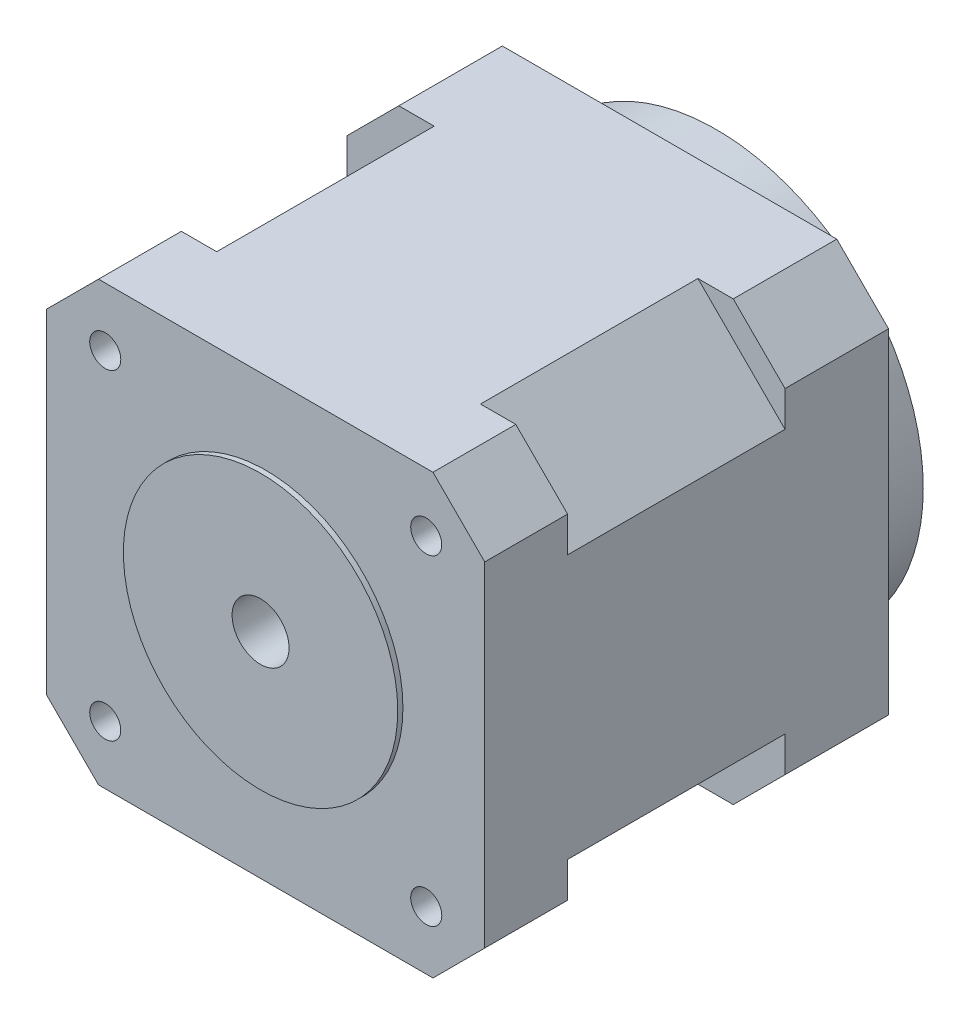
SolidWorks part; units mm, degrees
ref_plane "Front Plane" through (0, 0, 0) normal (0, 0, 1) x (1, 0, 0)
ref_plane "Top Plane" through (0, 0, 0) normal (0, 1, 0) x (1, 0, 0)
ref_plane "Right Plane" through (0, 0, 0) normal (1, 0, 0) x (0, 0, -1)
sketch "Sketch2" plane through (0, 0, 0) normal (0, 0, 1) x (1, 0, 0)
  line L1 (-21.15, -21.15) -> (21.15, -21.15)
  line L2 (-21.15, -21.15) -> (-21.15, 21.15)
  line L3 (-21.15, 21.15) -> (21.15, 21.15)
  line L4 (21.15, -21.15) -> (21.15, 21.15)
  line L5 (-21.15, -21.15) -> (21.15, 21.15) construction
  line L6 (-21.15, 21.15) -> (21.15, -21.15) construction
  point P0 (0, 0)
  dimension "D1" = 42.3
  dimension "D2" = 42.3
extrude "Boss-Extrude5" add sketch "Sketch2" along normal blind 39
sketch "Sketch3" plane through (0, 0, 39) normal (0, 0, 1) x (1, 0, 0)
  line L0 (21.15, -21.15) -> (-21.15, 21.15) construction
  line L1 (-21.15, -21.15) -> (21.15, 21.15) construction
  line L2 (-21.15, 21.15) -> (-21.15, 12.7386)
  line L3 (-21.15, 21.15) -> (-21.15, -21.15) construction
  line L4 (-21.15, 12.7386) -> (-16.9443, 16.9443)
  line L5 (-16.9443, 16.9443) -> (-12.7386, 21.15)
  line L6 (21.15, 21.15) -> (-21.15, 21.15) construction
  line L7 (-12.7386, 21.15) -> (-21.15, 21.15)
  line L8 (21.15, -12.7386) -> (21.15, -21.15)
  line L9 (12.7386, -21.15) -> (16.9443, -16.9443)
  line L10 (21.15, -21.15) -> (12.7386, -21.15)
  line L11 (16.9443, -16.9443) -> (21.15, -12.7386)
  line L12 (0, 0) -> (0, 13.988) construction
  line L13 (12.7386, 21.15) -> (21.15, 21.15)
  line L14 (16.9443, 16.9443) -> (12.7386, 21.15)
  line L15 (21.15, 12.7386) -> (16.9443, 16.9443)
  line L16 (21.15, 21.15) -> (21.15, 12.7386)
  line L17 (0, 0) -> (-10.5337, 0) construction
  line L18 (-12.7386, -21.15) -> (-21.15, -21.15)
  line L19 (-16.9443, -16.9443) -> (-12.7386, -21.15)
  line L20 (-21.15, -12.7386) -> (-16.9443, -16.9443)
  line L21 (-21.15, -21.15) -> (-21.15, -12.7386)
  point P5 (0, 0)
  point P10 (0, 0)
chamfer "Chamfer4" distance 5 angle 45 4 edges at (21.15, -21.15, 19.5) (-21.15, -21.15, 19.5) (-21.15, 21.15, 19.5) (21.15, 21.15, 19.5)
extrude "Cut-Extrude1" cut sketch "Sketch3" against normal blind 21 from offset 8 offset against normal yes
sketch "Sketch5" plane through (0, 0, 0) normal (0, 0, -1) x (-1, 0, 0)
  circle A0 centre (0, 0) radius 20
  dimension "D1" = 40
extrude "Boss-Extrude6" add sketch "Sketch5" along normal blind 4.5
sketch "Sketch7" plane through (0, 0, 39) normal (0, 0, 1) x (1, 0, 0)
  line L0 (0, -16.5238) -> (0, 16.5238) construction
  line L1 (-16.318, 0) -> (16.318, 0) construction
  circle A0 centre (-15.5, 15.5) radius 1.5
  circle A1 centre (-15.5, -15.5) radius 1.5
  circle A2 centre (15.5, 15.5) radius 1.5
  circle A3 centre (15.5, -15.5) radius 1.5
  point P7 (0, 0)
  point P11 (0, 0)
  dimension "D1" = 3
  dimension "D2" = 15.5
  dimension "D3" = 15.5
extrude "Cut-Extrude3" cut sketch "Sketch7" against normal blind 4.5
sketch "Sketch8" plane through (0, 0, 39) normal (0, 0, 1) x (1, 0, 0)
  circle A0 centre (0, 0) radius 13.2479
extrude "Boss-Extrude7" add sketch "Sketch8" along normal blind 0.5
sketch "Sketch6" plane through (0, 0, 39) normal (0, 0, 1) x (1, 0, 0)
  circle A0 centre (0, 0) radius 2.75
  dimension "D1" = 5.5
extrude "Cut-Extrude2" cut sketch "Sketch6" against normal blind 4.5 and the other way through all
